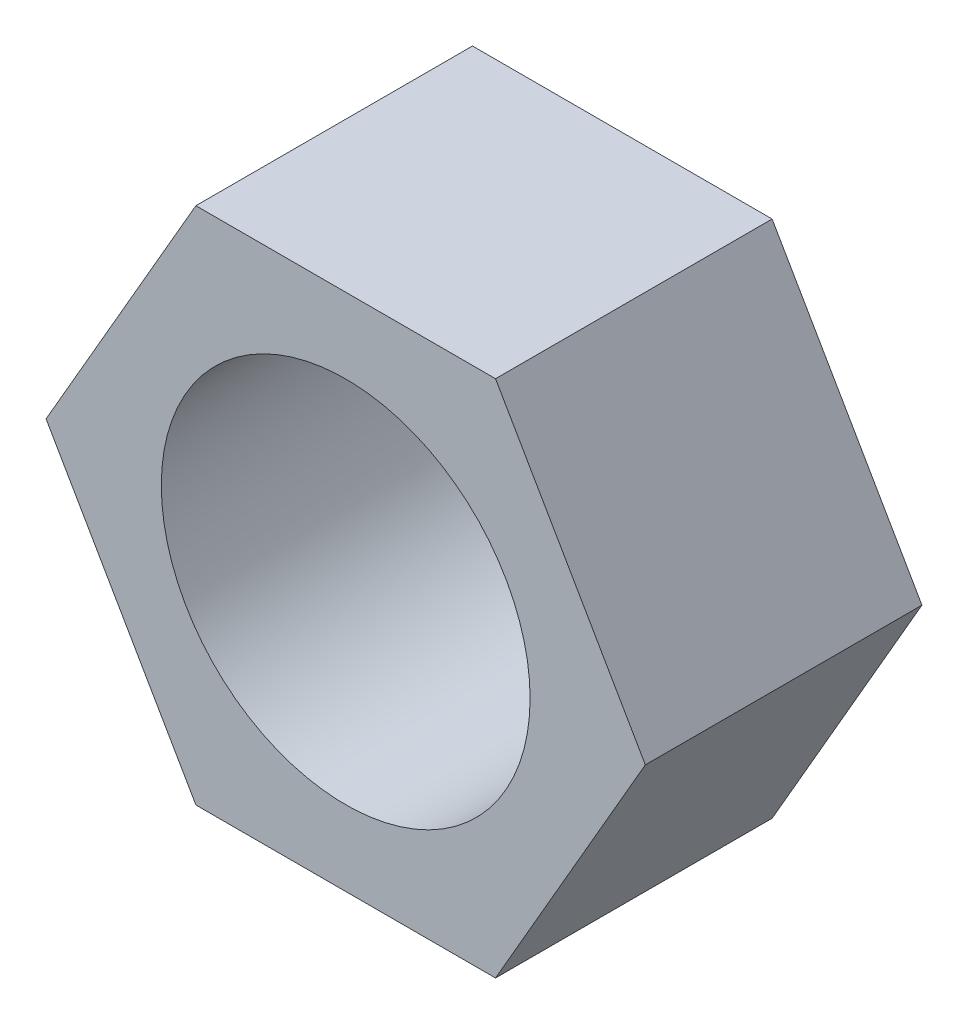
SolidWorks part; units mm, degrees
ref_plane "前视基准面" through (0, 0, 0) normal (0, 0, 1) x (1, 0, 0)
ref_plane "上视基准面" through (0, 0, 0) normal (0, 1, 0) x (1, 0, 0)
ref_plane "右视基准面" through (0, 0, 0) normal (1, 0, 0) x (0, 0, -1)
other "Configuration Table"
sketch "Sketch1" plane through (0, 0, 0) normal (0, 0, 1) x (1, 0, 0)
  line L1 (6.5, 0) -> (3.25, 5.6292)
  line L2 (3.25, 5.6292) -> (-3.25, 5.6292)
  line L3 (-3.25, 5.6292) -> (-6.5, 0)
  line L4 (-6.5, 0) -> (-3.25, -5.6292)
  line L5 (-3.25, -5.6292) -> (3.25, -5.6292)
  line L6 (3.25, -5.6292) -> (6.5, 0)
  circle A0 centre (0, 0) radius 5.6292 construction
extrude "Boss-Extrude1" add sketch "Sketch1" along normal blind 6
sketch "Sketch2" plane through (0, 0, 0) normal (0, 0, 1) x (1, 0, 0)
  circle A0 centre (0, 0) radius 4
extrude "Cut-Extrude1" cut sketch "Sketch2" along normal blind 6
sketch3d "3DSketch1"
  line L0 (0, 0, 0) -> (0, 0, 1000) construction
ref_axis "nut_axis" through (0, 0, 0) along (0, 0, 1)
ref_plane "bottom_face" through (0, 0, 0) normal (0, 0, 1) x (1, 0, 0)
ref_plane "top_face" through (0, 0, 6) normal (0, 0, 1) x (1, 0, 0)
